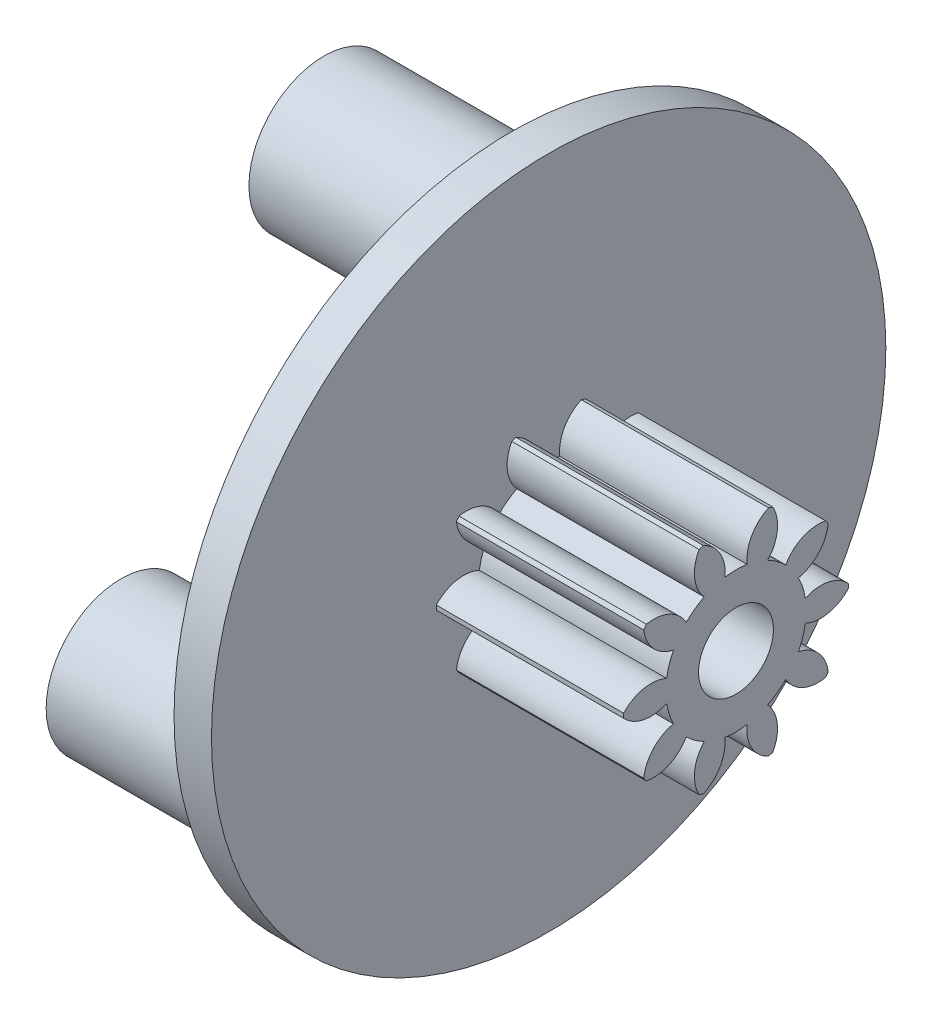
SolidWorks part; units mm, degrees
ref_plane "Plane1" through (0, 0, 0) normal (0, 0, 1) x (1, 0, 0)
ref_plane "Plane2" through (0, 0, 0) normal (0, 1, 0) x (1, 0, 0)
ref_plane "Plane3" through (0, 0, 0) normal (1, 0, 0) x (0, 0, -1)
other "Configuration Table"
sketch "HoldingSke" plane through (0, 0, 0) normal (0, 1, 0) x (1, 0, 0)
  line L0 (0, 0) -> (1.9696, -0.3473)
  line L1 (-15, 0) -> (100, 0) construction
  line L2 (0, 0) -> (-2.1039, 2.3779)
  line L3 (0, 0) -> (-11.863, 4.5341)
  line L4 (0, 0) -> (8.5048, 1.4996)
  line L5 (0, 0) -> (-46.8476, -17.4728)
  line L6 (0, 0) -> (-4.1448, -2.7965)
  line L7 (-2.1039, 2.3779) -> (8.6587, 51.2066)
  line L8 (-76.2, 54.61) -> (-76, 54.61)
  line L9 (-71.009, 38.7566) -> (-53.1078, 45.2721)
  line L10 (-76.2, 71.12) -> (104.1128, 71.12)
  line L11 (0, 0) -> (-5, 0)
  line L12 (-76.2, 101.6) -> (-76.181, 101.6)
  line L13 (24.9733, 27.94) -> (52.9518, 28.4284)
  line L14 (24.9733, 27.94) -> (24.9743, 27.94)
  line L15 (24.9733, 27.94) -> (100.4006, 29.5858)
  line L16 (-63.627, -0.5) -> (-12.827, -0.5)
  circle A0 centre (0, 0) radius 0.75
  circle A1 centre (0, 0) radius 1.874
  circle A2 centre (0, 0) radius 37.5
  circle A3 centre (0, 0) radius 0.75
  dimension "Num_teeth" = 10
  dimension "Pitch_radius" = 180.3128
  dimension "Width" = 5
  dimension "Thickness" = 5
sketch "BasProSke" plane through (0, 0, 0) normal (0, 1, 0) x (1, 0, 0)
  line L0 (-10, 0) -> (60, 0) construction
  line L1 (0, 0) -> (0, 3)
  line L2 (0, 0) -> (5, 0)
  line L3 (5, 0) -> (5, 3)
  line L4 (5, 3) -> (0, 3)
  dimension "Thickness" = 5
  dimension "Diameter" = 6
revolve "Base-Revolve" add sketch "BasProSke" angle 360 about L0
sketch "TooCutSke" plane through (0, 0, 0) normal (1, 0, 0) x (0, 0, -1)
  line L1 (0, 0) -> (0, 107) construction
  line L2 (0, 0) -> (-0.4243, 2.4637) construction
  line L3 (0, 0) -> (-1.5292, 4.7063) construction
  line L4 (-0.4243, 2.4637) -> (-0.7646, 2.3532) construction
  arc A0 (0.2964, 1.8504) -> (-0.2964, 1.8504) centre (0, 0) ccw
  arc A1 (0.9059, 2.8866) -> (-0.9059, 2.8866) centre (0, 0) ccw
  circle A2 centre (0, 0) radius 2.5 construction
  circle A3 centre (0, 0) radius 2.3492 construction
  arc A4 (-0.2964, 1.8504) -> (-0.9059, 2.8866) centre (-1.2901, 1.9633) ccw
  arc A5 (0.9059, 2.8866) -> (0.2964, 1.8504) centre (1.2901, 1.9633) ccw
extrude "ToothCut" cut sketch "TooCutSke" along normal through all
fillet "Breaks" [suppressed] radius 0.01 tangent propagation no
fillet "RootFillets" [suppressed] radius 0.126
pattern_circular "TeethCuts" count 10 every 36 about axis through (-10, 0, 0) along (1, 0, 0) of "ToothCut", "RootFillets", "Breaks"
sketch "HubNeaOneSke" plane through (0, 0, 0) normal (-1, 0, 0) x (0, 0, 1)
  circle A0 centre (0, 0) radius 1.874
  dimension "Diameter" = 3.748
extrude "HubNearOne" [suppressed] add sketch "HubNeaOneSke" along normal blind 45.0008
sketch "HubNeaBotSke" plane through (0, 0, 0) normal (-1, 0, 0) x (0, 0, 1)
  circle A0 centre (0, 0) radius 1.874
  dimension "Diameter" = 3.748
extrude "HubNearBoth" [suppressed] add sketch "HubNeaBotSke" along normal blind 22.5004
ref_plane "FarPln" through (5, 0, 0) normal (1, 0, 0) x (0, 0, -1)
sketch "HubFarSke" plane through (5, 0, 0) normal (1, 0, 0) x (0, 0, -1)
  circle A0 centre (0, 0) radius 1.874
  dimension "Diameter" = 3.748
extrude "HubFar" [suppressed] add sketch "HubFarSke" along normal blind 22.5004
sketch "BorSke" plane through (0, 0, 0) normal (1, 0, 0) x (0, 0, -1)
  circle A0 centre (0, 0) radius 1
  dimension "Diameter" = 2
extrude "Bore" cut sketch "BorSke" along normal mid plane 100.0015
sketch "KeySke" plane through (0, 0, 0) normal (1, 0, 0) x (0, 0, -1)
  line L0 (-0.3, 0) -> (-0.3, 0.95)
  line L1 (-0.3, 0.95) -> (0.3, 0.95)
  line L2 (0.3, 0.95) -> (0.3, 0)
  line L3 (0, 0) -> (0, 34) construction
  line L4 (-0.3, 0) -> (0.3, 0)
  dimension "Width" = 0.6
extrude "Keyway" [suppressed] cut sketch "KeySke" along normal mid plane 100.0015
pattern_circular "Keyway2" [suppressed] count 2 every 90 about axis through (-10, 0, 0) along (1, 0, 0) reverse direction yes
sketch "草图1" plane through (0, 0, 0) normal (-1, 0, 0) x (0, 0, 1)
  circle A0 centre (0, 0) radius 9
  circle A1 centre (0, 0) radius 1.5
  circle A2 centre (0, 6.25) radius 2
  circle A3 centre (5.4127, -3.125) radius 2
  circle A4 centre (-5.4127, -3.125) radius 2
  point P7 (0, 0)
  point P12 (0, 0)
  dimension "D1" = 3
  dimension "D2" = 18
  dimension "D3" = 4
  dimension "D4" = 6.25
  dimension "D5" = 3
extrude "凸台-拉伸1" add sketch "草图1" along normal blind 1 contours A0 | A1
extrude "凸台-拉伸2" add sketch "草图1<3>" along normal blind 5 from surface contours A2 | A4 | A3 region at (0, 6.25, 0) region at (0, -3.125, 5.4127) region at (0, -3.125, -5.4127) starting at face at (-1, 0, 9)
sketch "草图1<3>" plane through (0, 0, 0) normal (-1, 0, 0) x (0, 0, 1) same geometry as "草图1"
equation "' \"Module@HoldingSke\" = 6.35"
equation "' \"Num_teeth@HoldingSke\" = 12"
equation "' \"Ap@HoldingSke\" =  20"
equation "' \"Ap@HoldingSke\" = 20"
equation "' \"Width@HoldingSke\" = 0.5 * 25.4"
equation "' \"Hub_dia@HoldingSke\"= 1 * 25.4"
equation "' \"Hub_dia@HoldingSke\" = 1 * 25.4"
equation "' \"Overall_len@HoldingSke\" = 1.0 * 25.4"
equation "' \"Bore@HoldingSke\" = 0.75 * 25.4"
equation "' \"T_dim@HoldingSke\" = 0.1 * 25.4"
equation "' \"Width@KeySke\" = 0.25 * 25.4"
equation "' \"Show_teeth@HoldingSke\" = 13"
equation "' \"Backlash@HoldingSke\" = 0.009 * 25.4"
equation "' \"Addendum_fac@HoldingSke\" = 1.0"
equation "' \"Dedendum_fac@HoldingSke\" = 1.25"
equation "' \"Dedendum_add@HoldingSke\" = 0.00005 * 25.4"
equation "' \"Clearance_fac@HoldingSke\" = 0.25"
equation "\"Pitch@HoldingSke\" = 1 / \"Module@HoldingSke\""
equation "\"Overcut_dia@TooCutSke\" = (\"Num_teeth@HoldingSke\" + 2 * \"Addendum_fac@HoldingSke\") / \"Pitch@HoldingSke\" + 0.002 * 25.4"
equation "\"Pitch_dia@TooCutSke\" = \"Num_teeth@HoldingSke\" / \"Pitch@HoldingSke\""
equation "\"Base_dia@TooCutSke\" = \"Num_teeth@HoldingSke\" / \"Pitch@HoldingSke\" * cos((\"Ap@HoldingSke\"  * 3.14159265 / 180))"
equation "\"Root_dia@TooCutSke\" = (\"Num_teeth@HoldingSke\" + 2) / \"Pitch@HoldingSke\" - 2 * (\"Addendum_fac@HoldingSke\" + \"Dedendum_fac@HoldingSke\") / \"Pitch@HoldingSke\" - \"Dedendum_add@HoldingSke\" * 2"
equation "\"Half_ang@TooCutSke\" = 180 / \"Num_teeth@HoldingSke\""
equation "\"Half_CT@TooCutSke\" = \"Num_teeth@HoldingSke\" / \"Pitch@HoldingSke\" * sin((3.14159265 / 2 / \"Num_teeth@HoldingSke\")) / 2 - 7 * \"Backlash@HoldingSke\" / 4"
equation "\"Flank_rad@TooCutSke\" = \"Num_teeth@HoldingSke\" / \"Pitch@HoldingSke\" / 5"
equation "\"Radius@RootFillets\" = \"Clearance_fac@HoldingSke\" / \"Pitch@HoldingSke\" + \"Dedendum_add@HoldingSke\""
equation "\"Break_rad@Breaks\" = 0.02 / \"Pitch@HoldingSke\""
equation "\"Thickness@HoldingSke\" = \"Width@HoldingSke\""
equation "\"OAL@HoldingSke\" = \"Thickness@HoldingSke\""
equation "\"MHD@HoldingSke\" = (\"Num_teeth@HoldingSke\" + 2) / \"Pitch@HoldingSke\" - 2 * (\"Addendum_fac@HoldingSke\" + \"Dedendum_fac@HoldingSke\")  / \"Pitch@HoldingSke\" - \"Dedendum_add@HoldingSke\" * 2"
equation "\"MBD@HoldingSke\" = (\"Num_teeth@HoldingSke\" + 2) / \"Pitch@HoldingSke\" - 2 * (\"Addendum_fac@HoldingSke\" + \"Dedendum_fac@HoldingSke\")  / \"Pitch@HoldingSke\" - \"Dedendum_add@HoldingSke\" * 2 - 0.002 * 25.4"
equation "\"MHD@HoldingSke\" = ((sgn( \"MHD@HoldingSke\" - \"Hub_dia@HoldingSke\" )-1)*( \"MHD@HoldingSke\" - \"Hub_dia@HoldingSke\" ))/-2+ \"Hub_dia@HoldingSke\""
equation "\"MBD@HoldingSke\" = ((sgn( \"MBD@HoldingSke\" - \"Bore@HoldingSke\" )-1)*( \"MBD@HoldingSke\" - \"Bore@HoldingSke\" ))/-2+ \"Bore@HoldingSke\""
equation "\"OAL@HoldingSke\" = ((sgn( \"OAL@HoldingSke\" - \"Overall_len@HoldingSke\" )+1)*( \"OAL@HoldingSke\" - \"Overall_len@HoldingSke\" ))/2 + \"Overall_len@HoldingSke\" + 0.000002 * 25.4"
equation "\"Num_teeth@TeethCuts\" = int( \"Show_teeth@HoldingSke\" ) + 1"
equation "\"Num_teeth@TeethCuts\" = ((sgn( \"Num_teeth@TeethCuts\" - \"Num_teeth@HoldingSke\" )-1)*( \"Num_teeth@TeethCuts\" - \"Num_teeth@HoldingSke\" ))/-2+ \"Num_teeth@HoldingSke\""
equation "\"Num_teeth@TeethCuts\" = ((sgn( \"Num_teeth@TeethCuts\" - 2.0)+1)*( \"Num_teeth@TeethCuts\" - 2.0))/2 +2.0"
equation "\"Angle@TeethCuts\" = 360.0 / \"Num_teeth@HoldingSke\""
equation "\"Diameter@BasProSke\" = (\"Num_teeth@HoldingSke\" + 2 * \"Addendum_fac@HoldingSke\") / \"Pitch@HoldingSke\""
equation "\"Thickness@BasProSke\"  = \"Thickness@HoldingSke\""
equation "' \"Fillet_rad@BasProSke\" =  \"Thickness@HoldingSke\" * 0.05"
equation "' \"Fillet_rad@BasProSke\" = \"Thickness@HoldingSke\" * 0.05"
equation "\"MHD@HoldingSke\" = ((sgn( \"MHD@HoldingSke\" - \"Root_dia@TooCutSke\" )-1)*( \"MHD@HoldingSke\" - \"Root_dia@TooCutSke\" ))/-2+ \"Root_dia@TooCutSke\""
equation "\"Diameter@HubNeaOneSke\" = \"MHD@HoldingSke\""
equation "\"Length@HubNearOne\" = \"OAL@HoldingSke\" - \"Thickness@BasProSke\""
equation "\"Diameter@HubNeaBotSke\" = \"MHD@HoldingSke\""
equation "\"Length@HubNearBoth\" = ( \"OAL@HoldingSke\" - \"Thickness@BasProSke\" ) / 2.0"
equation "\"Thickness@FarPln\" = \"Thickness@BasProSke\""
equation "\"Diameter@HubFarSke\" = \"MHD@HoldingSke\""
equation "\"Length@HubFar\" = ( \"OAL@HoldingSke\" - \"Thickness@BasProSke\" ) / 2.0"
equation "\"D1@Bore\"= \"OAL@HoldingSke\" * 2.0"
equation "\"D1@Keyway\" = \"OAL@HoldingSke\" * 2.0"
equation "\"Offset@KeySke\" = \"T_dim@HoldingSke\" + \"MBD@HoldingSke\" / 2.0"
